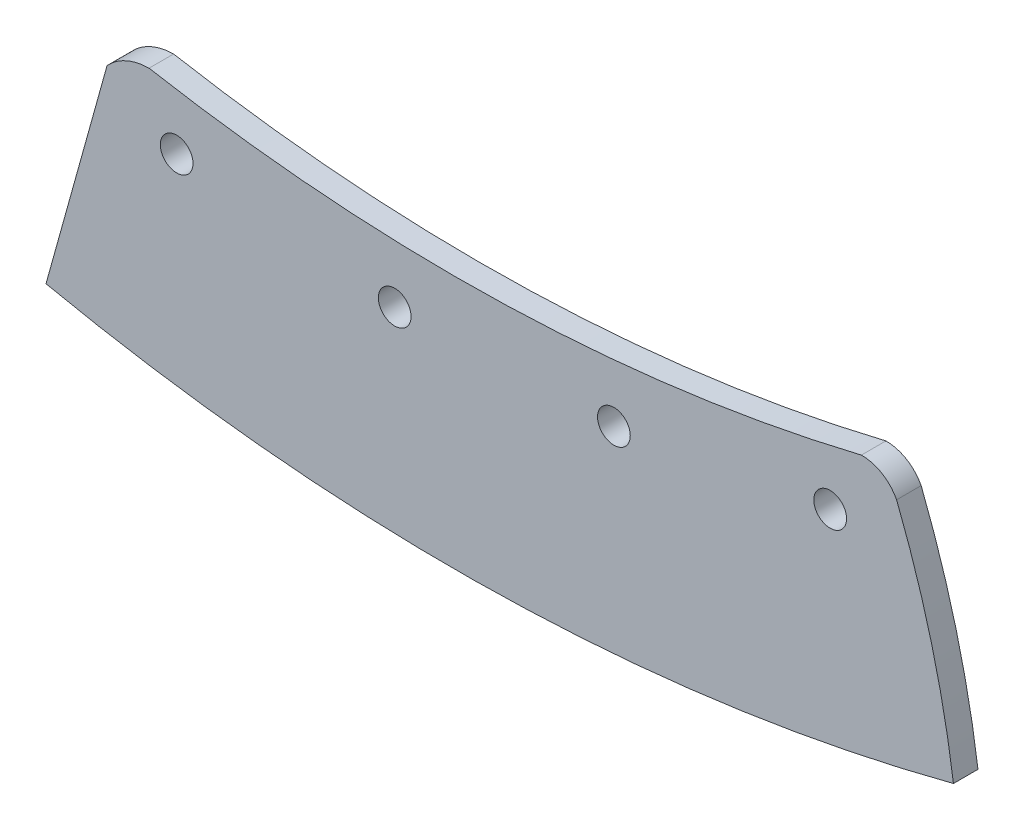
SolidWorks part; units mm, degrees
ref_plane "Ön Düzlem" through (0, 0, 0) normal (0, 0, 1) x (1, 0, 0)
ref_plane "Üst Düzlem" through (0, 0, 0) normal (0, 1, 0) x (1, 0, 0)
ref_plane "Sağ Düzlem" through (0, 0, 0) normal (1, 0, 0) x (0, 0, -1)
sketch "Çizim1" plane through (0, 0, 0) normal (0, 0, 1) x (1, 0, 0)
  line L0 (422.214, -123.931) -> (422.214, 89.1471) construction
  line L1 (-124.5538, 8.472) -> (348.2174, 107.3474) construction
  line L2 (0, 0) -> (10.508, 154.6434) construction
  line L3 (235.3458, 166.273) -> (265.9289, 16.3608) construction
  line L4 (89.2473, 151.971) -> (93.831, -2.9612) construction
  line L5 (-154.6986, 156.8575) -> (-192.025, 22.7093)
  circle A0 centre (-112.1839, 131.277) radius 10
  arc A1 (-112.1839, 131.277) -> (287.1405, 142.95) centre (59.4427, 1096.1927) ccw construction
  arc A2 (-129.0538, 168.2912) -> (306.2017, 181.1684) centre (58.1264, 1203.8653) ccw
  arc A3 (-192.025, 22.7093) -> (362.4651, 35.4976) centre (58.1264, 1203.8653) ccw
  circle A4 centre (21.041, 116.8852) radius 10
  circle A5 centre (154.9838, 120.8006) radius 10
  circle A6 centre (287.1405, 142.95) radius 10
  arc A7 (-154.6986, 156.8575) -> (-129.0538, 168.2912) centre (-128.6706, 132.9551) cw
  arc A8 (306.2017, 181.1684) -> (327.7382, 168.2912) centre (306.4346, 157.1101) cw
  arc A9 (327.7382, 168.2912) -> (362.4651, 35.4976) centre (-205.2551, -42.0298) cw
  arc A10 (-156.6233, 15.7628) -> (342.7404, 30.5367) centre (58.1264, 1203.8653) ccw construction
  dimension "D9" = 20
  dimension "D10" = 20
  dimension "D11" = 20
  dimension "D12" = 20
  dimension "D1" = 483
  dimension "D2" = 155
  dimension "D3" = 153
  dimension "D5" = 399.495
  dimension "D6" = 134
  dimension "D7" = 134
  dimension "D8" = 134
  dimension "D13" = 134.7648
  dimension "D14" = 131.2243
  dimension "D15" = 554.4901
  dimension "D4" = 155
base flange "Taban-Flanş1" sketch "Çizim1" thickness 15 reverse thickness direction no parameters "D1"=4
sketch "Büküm-Çizgileri1" [suppressed] plane through (0, 0, 0) normal (0, 1, 0) x (1, 0, 0)
sketch "Sınırlandırma-Kutusu1" [suppressed] plane through (0, 0, 0) normal (0, 1, 0) x (1, 0, 0)
sheet metal parameters "Sac-Levha1" thickness 15 parameters "D1"=4
flat pattern "Düz-Çoğaltma1" [suppressed]
sketch "Büküm-Çizgileri2" plane through (0, 0, 0) normal (0, 1, 0) x (1, 0, 0)
sketch3d "Sınırlandırma-Kutusu2" [suppressed]
  line L0 (-62.3477, -144.3292, 0) -> (492.0365, -127.9557, 0) construction
  line L1 (-67.5961, 33.3732, 0) -> (486.7881, 49.7467, 0) construction
  line L2 (-62.3477, -144.3292, 0) -> (-67.5961, 33.3732, 0) construction
  line L3 (492.0365, -127.9557, 0) -> (486.7881, 49.7467, 0) construction
